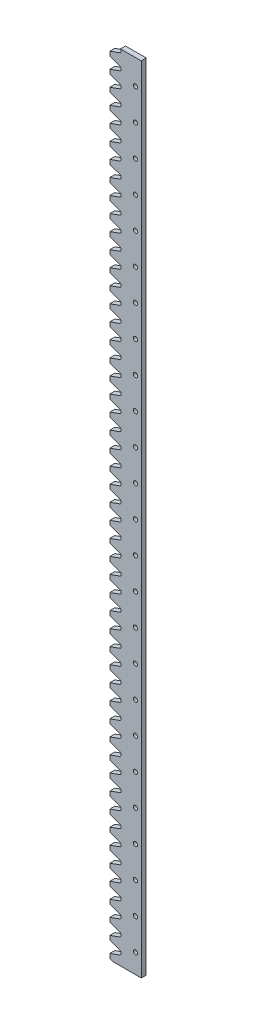
SolidWorks part; units mm, degrees
material "碳纤维"
ref_plane "Front" through (0, 0, 0) normal (0, 0, 1) x (1, 0, 0)
ref_plane "Top" through (0, 0, 0) normal (0, 1, 0) x (1, 0, 0)
ref_plane "Right" through (0, 0, 0) normal (1, 0, 0) x (0, 0, -1)
ref_axis "基准轴1" through (0, -50, 0) along (0, 1, 0)
sketch "SketchCI.m_strSketchName" plane through (0, 0, 0) normal (0, 0, 1) x (1, 0, 0)
  line L0 (-3, 4.7124) -> (-3, -560.7743)
  line L1 (-3, -560.7743) -> (19.05, -560.7743)
  line L2 (19.05, -560.7743) -> (19.05, 4.7124)
  line L3 (19.05, 4.7124) -> (-3, 4.7124)
  dimension "D1" = 3
  dimension "D2" = 560.7743
  dimension "D3" = 19.05
  dimension "D4" = 4.7124
extrude "拉伸CI" add sketch "SketchCI.m_strSketchName" along normal blind 1.5 and the other way blind 1.5
sketch "齿草图大直齿轮" plane through (0, 0, 0) normal (0, 0, 1) x (1, 0, 0)
  line L0 (-3, 3.4481) -> (-3, -3.4481)
  line L1 (-3, -3.4481) -> (3.1578, -1.2068)
  line L2 (3.75, -0.3611) -> (3.75, 0.3611)
  line L3 (3.1578, 1.2068) -> (-3, 3.4481)
  arc A0 (3.1578, -1.2068) -> (3.75, -0.3611) centre (2.85, -0.3611) ccw
  arc A1 (3.75, 0.3611) -> (3.1578, 1.2068) centre (2.85, 0.3611) ccw
  dimension "D1" = 1.8
  dimension "D2" = 1.8
  dimension "齿顶高" = 3
  dimension "FLANKONE" = 2.2141
  dimension "FLANKONEANGLE" = 70
  dimension "齿根高" = 3.75
  dimension "FLANKTWO" = 2.2141
  dimension "FLANKTWOANGLE" = 70
extrude "齿拉伸切除大直齿轮" cut sketch "齿草图大直齿轮" against normal blind 1.5 and the other way blind 1.5
pattern_linear "齿形大直齿轮" count 60 spacing 9.4248 along (0, -1, 0) of "齿拉伸切除大直齿轮"
sketch "辅助草图大直齿轮" plane through (0, 0, 0) normal (0, 0, 1) x (1, 0, 0)
  line L0 (0, 0) -> (0, -565.4867) construction
sketch "草图1" plane through (0, 0, 1.5) normal (0, 0, 1) x (1, 0, 0)
  line L0 (-3, -7.8572) -> (19.05, -7.8572)
  line L2 (19.05, -560.7743) -> (19.05, 4.7124) construction
  line L3 (0, 0) -> (0, -565.4867) construction
  line L4 (-3, -14.1372) -> (12.5, -14.1372) construction
  line L5 (-3, -12.8729) -> (-3, -15.4015) construction
  line L6 (-3, -7.8572) -> (-3, 4.7124)
  line L7 (-3, 4.7124) -> (19.05, 4.7124)
  line L8 (19.05, 4.7124) -> (19.05, -7.8572)
  line L9 (-3, -560.7743) -> (19.05, -560.7743)
  line L10 (19.05, -560.7743) -> (19.05, -506.8572)
  line L11 (19.05, -506.8572) -> (-3, -506.8572)
  line L12 (-3, -506.8572) -> (-3, -560.7743)
  circle A0 centre (12.5, -14.1372) radius 1.275
  circle A1 centre (12.5, -32.9772) radius 1.275
  circle A2 centre (12.5, -51.8172) radius 1.275
  circle A3 centre (12.5, -70.6572) radius 1.275
  circle A4 centre (12.5, -89.4972) radius 1.275
  circle A5 centre (12.5, -108.3372) radius 1.275
  circle A6 centre (12.5, -127.1772) radius 1.275
  circle A7 centre (12.5, -146.0172) radius 1.275
  circle A8 centre (12.5, -164.8572) radius 1.275
  circle A9 centre (12.5, -183.6972) radius 1.275
  circle A10 centre (12.5, -202.5372) radius 1.275
  circle A11 centre (12.5, -221.3772) radius 1.275
  circle A12 centre (12.5, -240.2172) radius 1.275
  circle A13 centre (12.5, -259.0572) radius 1.275
  circle A14 centre (12.5, -277.8972) radius 1.275
  circle A15 centre (12.5, -296.7372) radius 1.275
  circle A16 centre (12.5, -315.5772) radius 1.275
  circle A17 centre (12.5, -334.4172) radius 1.275
  circle A18 centre (12.5, -353.2572) radius 1.275
  circle A19 centre (12.5, -372.0972) radius 1.275
  circle A20 centre (12.5, -390.9372) radius 1.275
  circle A21 centre (12.5, -409.7772) radius 1.275
  circle A22 centre (12.5, -428.6172) radius 1.275
  circle A23 centre (12.5, -447.4572) radius 1.275
  circle A24 centre (12.5, -466.2972) radius 1.275
  circle A25 centre (12.5, -485.1372) radius 1.275
  circle A26 centre (12.5, -503.9772) radius 1.275
  dimension "D3" = 2.55
  dimension "D6" = 18.84
  dimension "D1" = 12.5
  dimension "D2" = 6.28
  dimension "D4" = 499
  dimension "D5" = 27
extrude "切除-拉伸1" cut sketch "草图1" against normal through all
sketch "草图2" plane through (0, 0, 1.5) normal (0, 0, 1) x (1, 0, 0)
  line L0 (16, -7.8572) -> (19.05, -7.8572)
  line L1 (2.1666, -7.8572) -> (19.05, -7.8572) construction
  line L2 (19.05, -7.8572) -> (19.05, -506.8572)
  line L3 (19.05, -506.8572) -> (16, -506.8572)
  line L4 (19.05, -506.8572) -> (0.7565, -506.8572) construction
  line L5 (16, -506.8572) -> (16, -7.8572)
  circle A0 centre (12.5, -14.1372) radius 1.275 construction
  dimension "D1" = 3.5
extrude "切除-拉伸2" cut sketch "草图2" against normal blind 10
sketch "草图3" plane through (0, 0, 1.5) normal (0, 0, 1) x (1, 0, 0)
  line L0 (2.1666, -7.8572) -> (16, -7.8572) construction
  line L1 (21.8944, -17.8572) -> (-13.954, -17.8572)
  line L2 (21.8944, -17.8572) -> (21.8944, -3.1388)
  line L3 (21.8944, -3.1388) -> (-13.954, -3.1388)
  line L4 (-13.954, -17.8572) -> (-13.954, -3.1388)
  line L5 (3.9702, -3.1388) -> (3.9702, -17.8572) construction
  line L6 (21.8944, -10.498) -> (-13.954, -10.498) construction
  line L7 (16, -506.8572) -> (0.7565, -506.8572) construction
  line L8 (25.906, -547.8187) -> (-14.1998, -547.8187)
  line L9 (25.906, -547.8187) -> (25.906, -496.8572)
  line L10 (25.906, -496.8572) -> (-14.1998, -496.8572)
  line L11 (-14.1998, -547.8187) -> (-14.1998, -496.8572)
  line L12 (5.8531, -496.8572) -> (5.8531, -547.8187) construction
  line L13 (25.906, -522.3379) -> (-14.1998, -522.3379) construction
  point P0 (3.9702, -10.498)
  point P6 (5.8531, -522.3379)
  point P12 (21.8944, -17.8572)
  dimension "D1" = 10
  dimension "D2" = 10
extrude "切除-拉伸3" cut sketch "草图3" against normal blind 10
